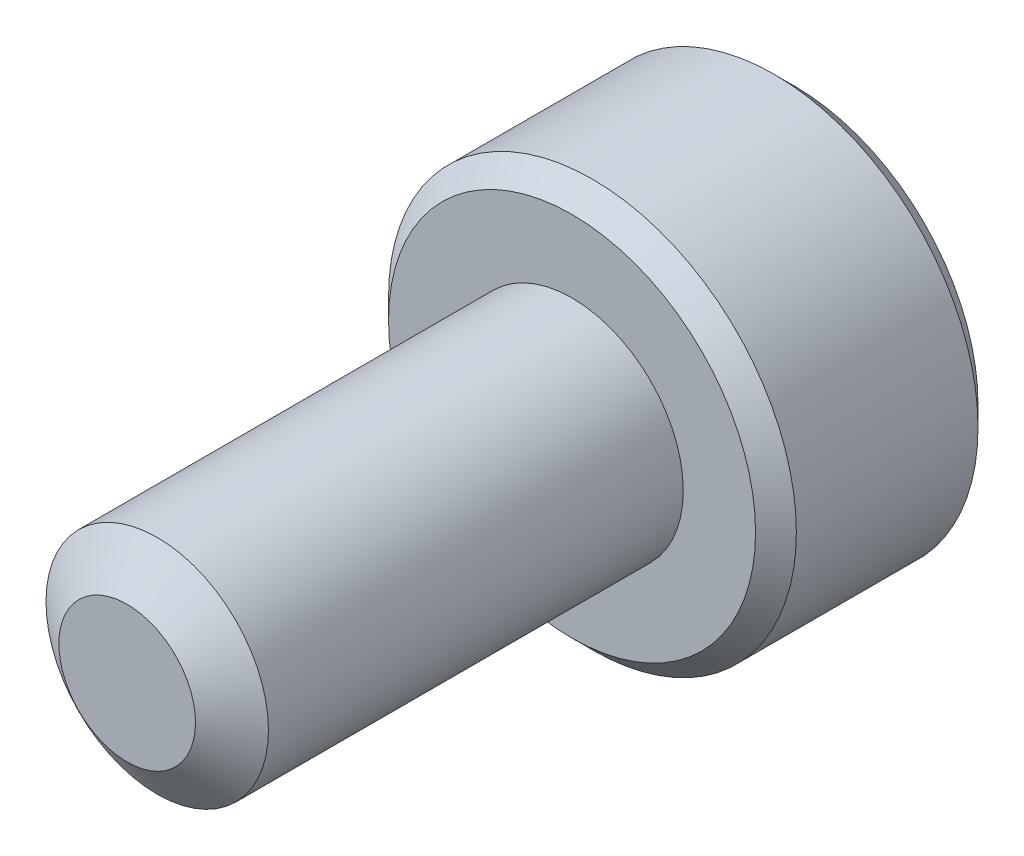
SolidWorks part; units mm, degrees
other "DetailItem1"
material "1.4310 (X10CrNi18-8)"
ref_plane "Front Plane" through (0, 0, 0) normal (0, 0, 1) x (1, 0, 0)
ref_plane "Top Plane" through (0, 0, 0) normal (0, 1, 0) x (1, 0, 0)
ref_plane "Right Plane" through (0, 0, 0) normal (1, 0, 0) x (0, 0, -1)
sketch "Sketch1" plane through (0, 0, 0) normal (0, 0, 1) x (1, 0, 0)
  circle A0 centre (0, 0) radius 1.5
  dimension "OD" = 3
extrude "Extrude1" add sketch "Sketch1" against normal blind 6
sketch "Sketch2" plane through (0, 0, 0) normal (0, 0, 1) x (1, 0, 0)
  circle A0 centre (0, 0) radius 1.5 construction
  circle A1 centre (0, 0) radius 1.5
curve "Helix/Spiral1" pitch 0.5 height 6.5 turns 13 parameters "pitch"=0.5
sketch "Sketch3" plane through (0, 0, 0) normal (1, 0, 0) x (0, 0, -1)
  line L0 (-0.4375, 1.5) -> (-0.25, 1.1752)
  line L1 (-0.25, 1.1752) -> (-0.1875, 1.1752)
  line L2 (-0.1875, 1.1752) -> (0, 1.5)
  line L3 (-0.4375, 1.5) -> (0, 1.5)
  line L4 (-0.2187, 1.5) -> (-0.2188, 1.1752) construction
  line L5 (-0.3438, 1.3376) -> (-0.0938, 1.3376) construction
  line L6 (0, 1.5) -> (0, -1.5) construction
  dimension "D1" = 0.0625
  dimension "D2" = 0.25
  dimension "D3" = 60
sweep "Cut-Sweep1" [suppressed] cut profiles "Sketch3" path "Helix/Spiral1"
sketch "Sketch4" plane through (0, 0, 0) normal (1, 0, 0) x (0, 0, -1)
  line L0 (0.4053, 1.5) -> (0, 0.9212)
  line L1 (0, 0.9212) -> (0, 1.5)
  line L2 (0.4053, 1.5) -> (0, 1.5)
  line L3 (-0.4375, 1.5) -> (0, 1.5) construction
  line L4 (0, 0) -> (7.0209, 0) construction
  dimension "D1" = 55
  dimension "D2" = 0.254
revolve "Cut-Revolve1" cut sketch "Sketch4" angle 360 about L4
sketch "Sketch6" plane through (0, 0, -6) normal (0, 0, -1) x (-1, 0, 0)
  circle A0 centre (0, 0) radius 2.75
  dimension "head dia" = 5.5
extrude "Extrude2" add sketch "Sketch6" along normal blind 3
sketch "Sketch7" plane through (0, 0, -9) normal (0, 0, -1) x (-1, 0, 0)
  line L1 (0, 1.4434) -> (-1.25, 0.7217)
  line L2 (-1.25, 0.7217) -> (-1.25, -0.7217)
  line L3 (-1.25, -0.7217) -> (0, -1.4434)
  line L4 (0, -1.4434) -> (1.25, -0.7217)
  line L5 (1.25, -0.7217) -> (1.25, 0.7217)
  line L6 (1.25, 0.7217) -> (0, 1.4434)
  circle A0 centre (0, 0) radius 1.25 construction
  dimension "hex dia" = 2.5
extrude "Cut-Extrude1" cut sketch "Sketch7" against normal blind 1.875
sketch "Sketch8" plane through (0, 0, -9) normal (0, 0, -1) x (-1, 0, 0)
  circle A0 centre (0, 0) radius 1.4434
extrude "Cut-Extrude2" cut sketch "Sketch8" against normal through all draft 45
chamfer "Chamfer1" distance 0.275 angle 45 2 edges at (-2.75, 0, -9) (-2.75, 0, -6)
sketch "Sketch10" plane through (0, 0, -6) normal (0, 0, 1) x (1, 0, 0)
  circle A1 centre (0, 0) radius 1.5
  circle A2 centre (0, 0) radius 1.5
  dimension "D1" = 0
ref_plane "Plane1" through (0, 0, 0) normal (0, 0, 1) x (1, 0, 0)
extrude "partial thread" [suppressed] add sketch "Sketch10" along normal up to surface (4 mm away) separate body up to plane "Plane1"
chamfer "Chamfer2" [suppressed] distance 0.06 angle 45
combine bodies "Combine1" [suppressed] operation type add bodies to combine 107 108
sketch "Sketch9" plane through (0, 0, 0) normal (1, 0, 0) x (0, 0, -1)
  line L0 (0, 1.5) -> (0, -1.5) construction
  line L1 (1.25, 1.5) -> (1.25, -1.5) construction
  dimension "D1" = 1.25
equation "\"D3@Helix/Spiral1\" = \"screw length@Extrude1\"+\"pitch@Helix/Spiral1\""
equation "\"D1@Sketch3\" = \"pitch@Helix/Spiral1\"*.125"
equation "\"D2@Sketch3\" = \"pitch@Helix/Spiral1\"*.5"
equation "\"D1@Cut-Extrude1\" = \"hex dia@Sketch7\"*.75"
equation "\"D1@Chamfer1\" = \"head dia@Sketch6\"*.05"
equation "\"D1@Sketch9\" = \"pitch@Helix/Spiral1\"*2.5"
equation "\"D1@Chamfer2\"=\"OD@Sketch1\"*.02"
